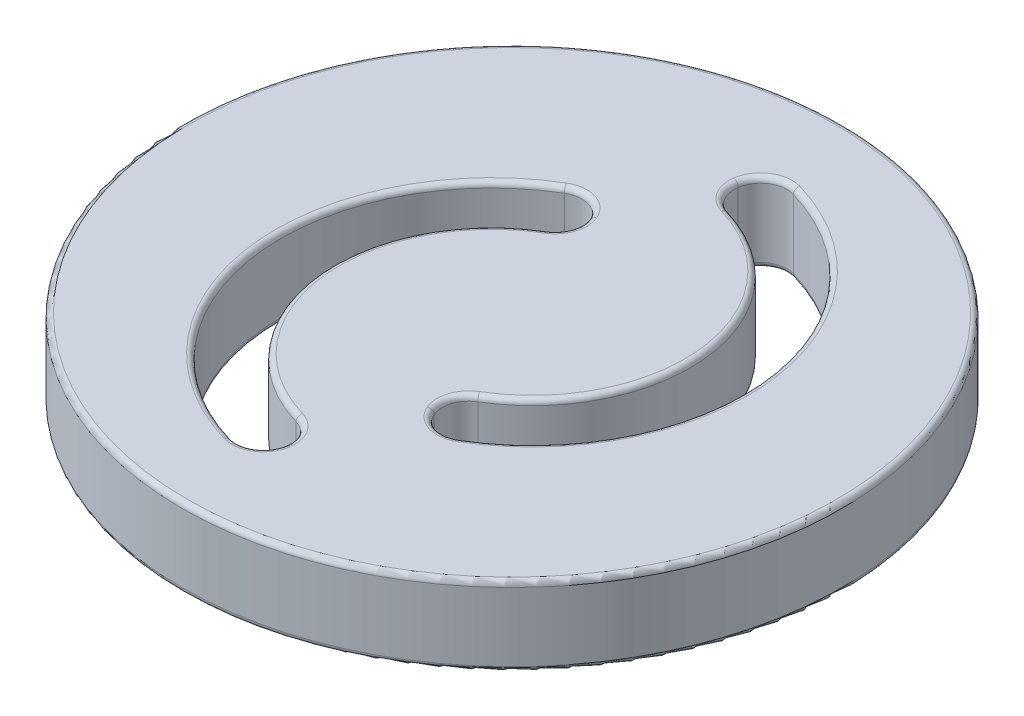
SolidWorks part; units mm, degrees
ref_plane "前视基准面" through (0, 0, 0) normal (0, 0, 1) x (1, 0, 0)
ref_plane "上视基准面" through (0, 0, 0) normal (0, 1, 0) x (1, 0, 0)
ref_plane "右视基准面" through (0, 0, 0) normal (1, 0, 0) x (0, 0, -1)
other "Configuration Table"
sketch "草图1" plane through (0, 0, 0) normal (0, 1, 0) x (1, 0, 0)
  circle A0 centre (0, 0) radius 125
  circle A1 centre (0, 0) radius 20
  dimension "D1" = 40
  dimension "D2" = 250
extrude "凸台-拉伸1" add sketch "草图1" along normal blind 30
sketch "草图2" plane through (0, 30, 0) normal (0, 1, 0) x (1, 0, 0)
  line L0 (0, 0) -> (0, 150) construction
  line L1 (0, 0) -> (-60.6659, 166.6783) construction
  line L2 (1.3957, 96.5021) -> (-1.3957, 76.6979)
  line L3 (13.256, -37.7534) -> (20.9461, -56.2159)
  line L6 (-13.256, 37.7534) -> (-20.9461, 56.2159)
  line L7 (-1.3957, -96.5021) -> (1.3957, -76.6979)
  arc A0 (0, 86.6) -> (17.101, -46.9846) centre (-9.7443, 17.4657) cw construction
  arc A1 (-1.3957, 76.6979) -> (13.256, -37.7534) centre (-9.7443, 17.4657) cw
  arc A2 (1.3957, 96.5021) -> (20.9461, -56.2159) centre (-9.7443, 17.4657) cw
  arc A3 (-1.3957, 76.6979) -> (13.256, -37.7534) centre (-9.7443, 17.4657) cw construction
  circle A4 centre (0, 0) radius 20 construction
  arc A5 (0, 86.6) -> (17.101, -46.9846) centre (-9.7443, 17.4657) cw construction
  arc A8 (-1.3957, -96.5021) -> (-20.9461, 56.2159) centre (9.7443, -17.4657) cw
  arc A9 (1.3957, -76.6979) -> (-13.256, 37.7534) centre (9.7443, -17.4657) cw
  arc A10 (0, -86.6) -> (-17.101, 46.9846) centre (9.7443, -17.4657) cw construction
  point P27 (0, 0)
  point P30 (1.3102, 1.6636)
  dimension "D1" = 20
  dimension "D2" = 86.6
  dimension "D3" = 50
  dimension "D4" = 10
  dimension "D5" = 10
  dimension "D6" = 2
extrude "切除-拉伸1" cut sketch "草图2" against normal blind 30
fillet "圆角3" radius 10 8 edges at (-20.9461, 15, -56.2159) (-13.256, 15, -37.7534) (-1.3957, 15, 96.5021) (1.3957, 15, 76.6979) (20.9461, 15, 56.2159) (13.256, 15, 37.7534) (-1.3957, 15, -76.6979) (1.3957, 15, -96.5021)
extrude "凸台-拉伸2" add sketch "草图1<3>" along normal up to surface (30 mm away) contours A1 region at (0, 0, 0) up to face at (-27.379, 30, 22.218)
sketch "草图1<3>" plane through (0, 0, 0) normal (0, 1, 0) x (1, 0, 0) same geometry as "草图1"
fillet "圆角4" radius 2 26 edges at (0, 0, 125) (22.9206, 0, 51.971) (16.5595, 0, 39.3402) (49.5892, 0, -25.0613) (1.4016, 0, -79.0657) (4.3758, 0, -92.8915) (69.4273, 0, -27.6009) (-69.4273, 0, 27.6009) (-22.9206, 0, -51.971) (-16.5595, 0, -39.3402) (-49.5892, 0, 25.0613) (-1.4016, 0, 79.0657) (-4.3758, 0, 92.8915) (0, 30, 125) (49.5892, 30, -25.0613) (16.5595, 30, 39.3402) (22.9206, 30, 51.971) (69.4273, 30, -27.6009) (4.3758, 30, -92.8915) (1.4016, 30, -79.0657) (-16.5595, 30, -39.3402) (-22.9206, 30, -51.971) (-69.4273, 30, 27.6009) (-4.3758, 30, 92.8915) (-1.4016, 30, 79.0657) (-49.5892, 30, 25.0613)
extrude "凸台-拉伸3" add sketch "草图1<4>" against normal blind 15 contours A1 region at (0, 0, 0)
sketch "草图1<4>" plane through (0, 0, 0) normal (0, 1, 0) x (1, 0, 0) same geometry as "草图1"
fillet "圆角5" radius 2 2 edges at (0, -15, 20) (0, 0, 20)
